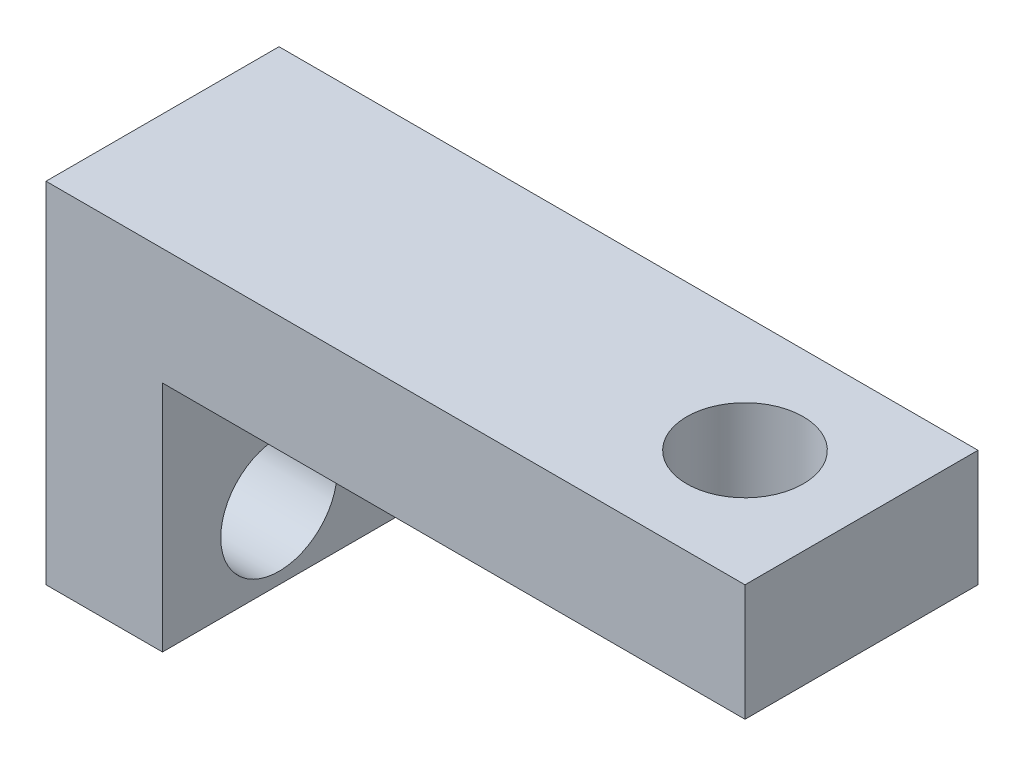
SolidWorks part; units mm, degrees
ref_plane "Plan de face" through (0, 0, 0) normal (0, 0, 1) x (1, 0, 0)
ref_plane "Plan de dessus" through (0, 0, 0) normal (0, 1, 0) x (1, 0, 0)
ref_plane "Plan de droite" through (0, 0, 0) normal (1, 0, 0) x (0, 0, -1)
sketch "Esquisse1" plane through (0, 0, 0) normal (0, 0, 1) x (1, 0, 0)
  line L0 (0, 0) -> (10, 0)
  line L1 (10, 0) -> (10, 20)
  line L2 (10, 20) -> (60, 20)
  line L3 (60, 20) -> (60, 30)
  line L4 (60, 30) -> (0, 30)
  line L5 (0, 30) -> (0, 0)
  dimension "D1" = 10
  dimension "D2" = 10
  dimension "D3" = 50
  dimension "D4" = 20
extrude "Boss.-Extru.1" add sketch "Esquisse1" along normal blind 10 and the other way blind 10
sketch "Esquisse2" plane through (0, 20, 0) normal (0, -1, 0) x (1, 0, 0)
  line L0 (60, -10) -> (60, 10) construction
  line L2 (10, -10) -> (60, -10) construction
  circle A0 centre (50, 0) radius 5
  dimension "D1" = 10
  dimension "D2" = 10
  dimension "D3" = 10
extrude "Enlèv. mat.-Extru.1" cut sketch "Esquisse2" against normal blind 10 contours A0
sketch "Esquisse3" plane through (0, 0, 0) normal (-1, 0, 0) x (0, 0, 1)
  line L0 (-10, 0) -> (10, 0) construction
  circle A0 centre (0, 6) radius 5
  dimension "D1" = 10
  dimension "D2" = 6
extrude "Enlèv. mat.-Extru.2" cut sketch "Esquisse3" against normal blind 10
